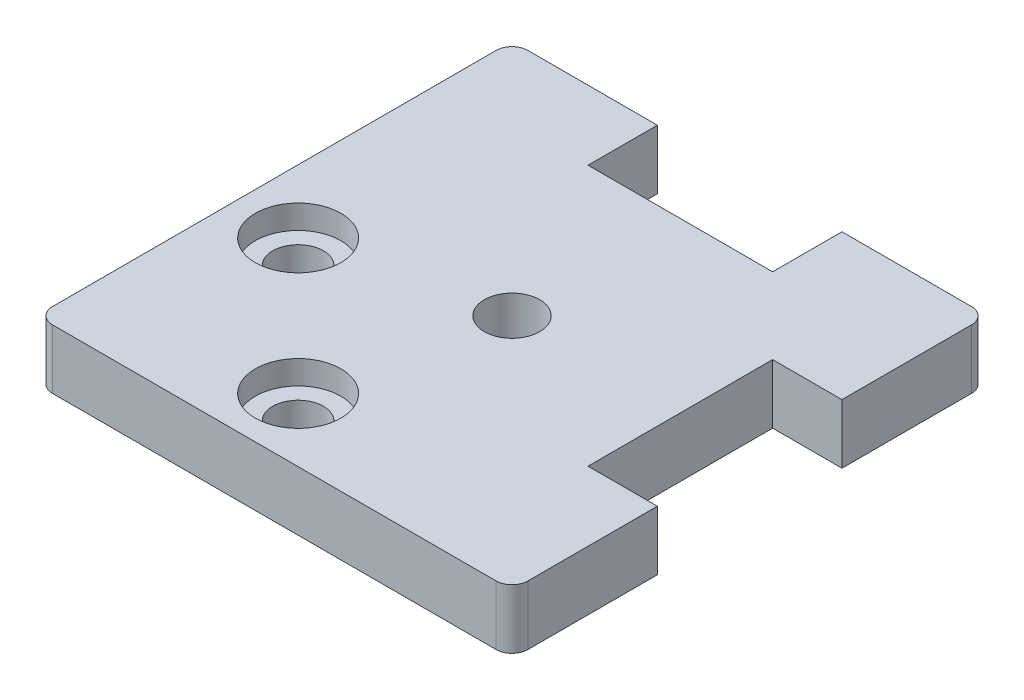
SolidWorks part; units mm, degrees
ref_plane "Front Plane" through (0, 0, 0) normal (0, 0, 1) x (1, 0, 0)
ref_plane "Top Plane" through (0, 0, 0) normal (0, 1, 0) x (1, 0, 0)
ref_plane "Right Plane" through (0, 0, 0) normal (1, 0, 0) x (0, 0, -1)
sketch "Sketch1" plane through (0, 0, 0) normal (0, 1, 0) x (1, 0, 0)
  line L1 (-38.1, 38.1) -> (38.1, 38.1)
  line L2 (-38.1, 38.1) -> (-38.1, -38.1)
  line L3 (-38.1, -38.1) -> (38.1, -38.1)
  line L4 (38.1, 38.1) -> (38.1, -38.1)
  line L5 (-38.1, 38.1) -> (38.1, -38.1) construction
  line L6 (-38.1, -38.1) -> (38.1, 38.1) construction
  point P0 (0, 0)
  dimension "D1" = 76.2
extrude "Boss-Extrude1" add sketch "Sketch1" along normal blind 9.525
sketch "Sketch6" plane through (0, 0, 0) normal (0, 1, 0) x (1, 0, 0)
  line L0 (38.1, 38.1) -> (-38.1, 38.1) construction
  line L1 (-38.1, 38.1) -> (-38.1, -38.1) construction
  line L2 (38.1, -38.1) -> (38.1, 38.1) construction
  line L3 (-38.1, -38.1) -> (38.1, -38.1) construction
  circle A0 centre (-28.575, 28.575) radius 3.81
  circle A1 centre (28.575, -28.575) radius 3.81
  dimension "D2" = 7.62
  dimension "D1" = 9.525
  dimension "D3" = 9.525
  dimension "D4" = 9.525
  dimension "D5" = 9.525
extrude "Cut-Extrude2" cut sketch "Sketch6" along direction (0, 1, 0) on the side of the normal blind 2.54 draft 30
sketch "Sketch7" plane through (0, 0, 0) normal (0, 1, 0) x (1, 0, 0)
  line L2 (-38.1, 38.1) -> (-38.1, -38.1) construction
  line L3 (-38.1, -38.1) -> (38.1, -38.1) construction
  circle A0 centre (-27.94, -27.94) radius 4.445
  dimension "D3" = 8.89
  dimension "D2" = 10.16
  dimension "D1" = 10.16
sketch "Sketch12" plane through (0, 9.525, 0) normal (0, 1, 0) x (1, 0, 0)
  line L2 (-38.1, -38.1) -> (38.1, -38.1) construction
  line L3 (-38.1, 38.1) -> (-38.1, -38.1) construction
  circle A0 centre (-27.94, -6.35) radius 4.064
  circle A1 centre (-6.35, -27.94) radius 4.064
  dimension "D2" = 10.16
  dimension "D3" = 8.128
  dimension "D4" = 31.75
  dimension "D5" = 10.16
  dimension "D1" = 31.75
extrude "Cut-Extrude4" cut sketch "Sketch12" against normal up to next
sketch "Sketch13" plane through (0, 9.525, 0) normal (0, -1, 0) x (1, 0, 0)
  circle A6 centre (-27.94, 6.35) radius 6.858
  circle A9 centre (-6.35, 27.94) radius 6.858
  dimension "D1" = 13.716
  dimension "D2" = 13.716
extrude "Cut-Extrude7" cut sketch "Sketch13" along normal blind 3.81
extrude "Cut-Extrude8" cut sketch "Sketch7" along normal blind 3.81 draft 45
ref_axis "Axis1" through (-6.35, -9.5852, 27.94) along (0, 1, 0)
ref_axis "Axis2" through (-27.94, -15.4165, 6.35) along (0, 1, 0)
sketch "Sketch15" plane through (0, 9.525, 0) normal (0, 1, 0) x (1, 0, 0)
  circle A4 centre (0, 0) radius 4.445
  dimension "D1" = 8.89
extrude "Cut-Extrude9" cut sketch "Sketch15" against normal up to next
fillet "Fillet1" radius 2.54 4 edges at (38.1, 4.7625, -38.1) (38.1, 4.7625, 38.1) (-38.1, 4.7625, 38.1) (-38.1, 4.7625, -38.1)
sketch "Sketch16" plane through (0, 0, 0) normal (0, -1, 0) x (1, 0, 0)
  line L0 (0, 0) -> (0, -38.1) construction
  line L1 (35.56, -38.1) -> (-35.56, -38.1) construction
  line L2 (0, 0) -> (38.1, 0) construction
  line L3 (38.1, 35.56) -> (38.1, -35.56) construction
  line L4 (-14.7955, -38.1) -> (14.7955, -38.1)
  line L5 (14.7955, -38.1) -> (14.7955, -26.9875)
  line L6 (14.7955, -26.9875) -> (-14.7955, -26.9875)
  line L7 (-14.7955, -26.9875) -> (-14.7955, -38.1)
  line L8 (38.1, -14.7955) -> (38.1, 14.7955)
  line L9 (38.1, 14.7955) -> (26.9875, 14.7955)
  line L10 (26.9875, 14.7955) -> (26.9875, -14.7955)
  line L11 (26.9875, -14.7955) -> (38.1, -14.7955)
  point P11 (0, -38.1)
  point P16 (38.1, 0)
  dimension "D1" = 29.591
  dimension "D2" = 29.591
  dimension "D3" = 11.1125
  dimension "D4" = 11.1125
extrude "Cut-Extrude10" cut sketch "Sketch16" against normal up to next
